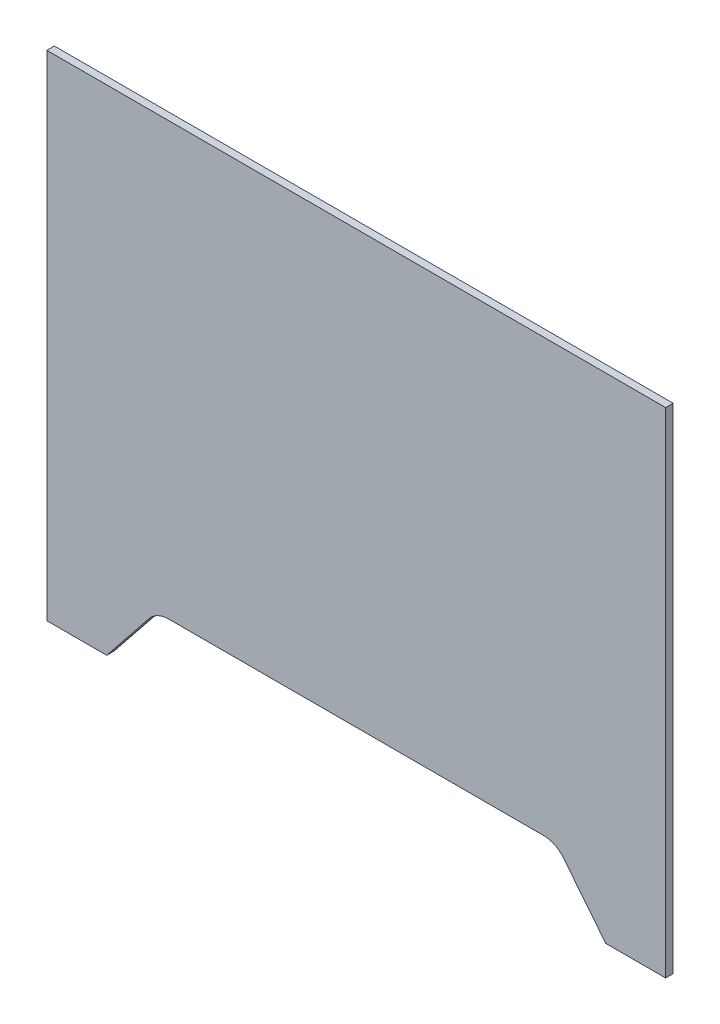
SolidWorks part; units mm, degrees
ref_plane "前视基准面" through (0, 0, 0) normal (0, 0, 1) x (1, 0, 0)
ref_plane "上视基准面" through (0, 0, 0) normal (0, 1, 0) x (1, 0, 0)
ref_plane "右视基准面" through (0, 0, 0) normal (1, 0, 0) x (0, 0, -1)
sketch "Sketch1" plane through (0, 0, 0) normal (0, 0, 1) x (1, 0, 0)
  line L0 (0, -99) -> (0, 0) construction
  line L1 (-124, -99) -> (124, -99) construction
  line L2 (-124, -99) -> (-124, 99)
  line L3 (-124, 99) -> (124, 99)
  line L4 (124, -99) -> (124, 99)
  line L5 (-124, -99) -> (124, 99) construction
  line L6 (-124, 99) -> (124, -99) construction
  line L7 (-75.1938, -74) -> (75.1938, -74)
  line L8 (83.0024, -77.753) -> (100, -99)
  line L9 (100, -99) -> (124, -99)
  line L10 (-100, -99) -> (-124, -99)
  line L11 (-83.0024, -77.753) -> (-100, -99)
  arc A0 (83.0024, -77.753) -> (75.1938, -74) centre (75.1938, -84) ccw
  arc A1 (-83.0024, -77.753) -> (-75.1938, -74) centre (-75.1938, -84) cw
  point P0 (0, 0)
  point P13 (80, -74)
  point P18 (0, -74)
  dimension "D6" = 10
  dimension "D1" = 248
  dimension "D2" = 198
  dimension "D3" = 25
  dimension "D4" = 24
  dimension "D5" = 80
extrude "Boss-Extrude1" add sketch "Sketch1" along normal blind 3
